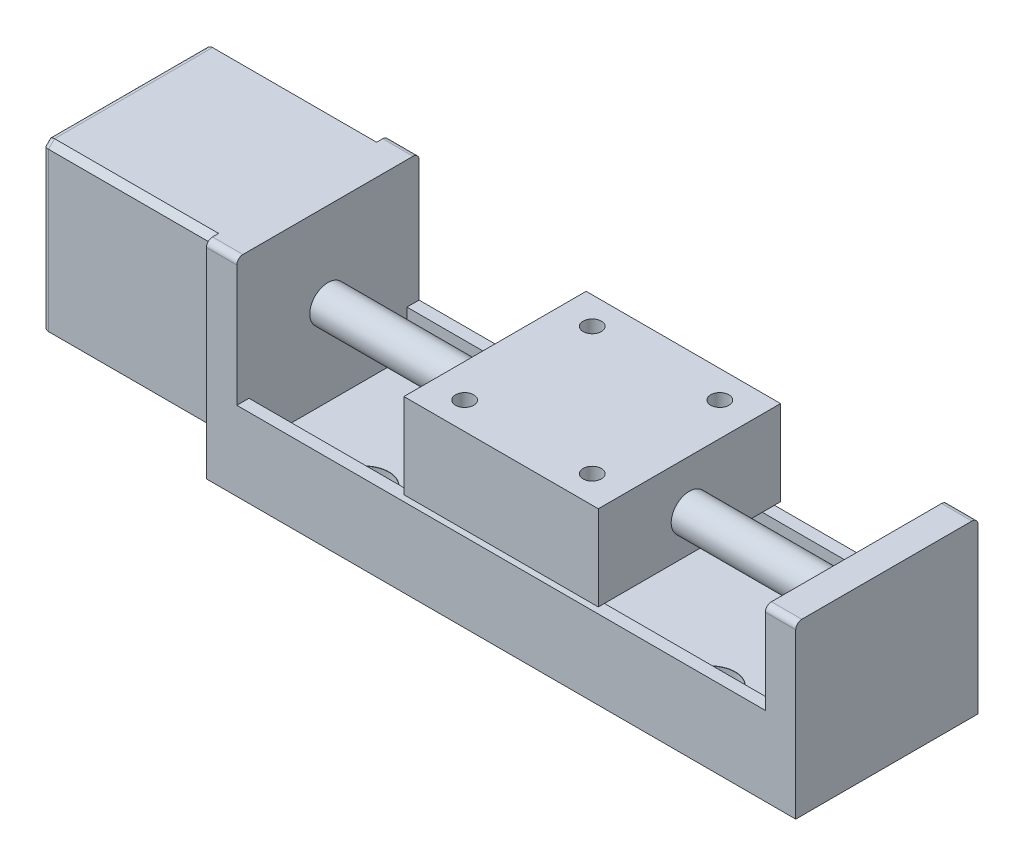
SolidWorks part; units mm, degrees
material "1060 Alloy"
ref_plane "Front Plane" through (0, 0, 0) normal (0, 0, 1) x (1, 0, 0)
ref_plane "Top Plane" through (0, 0, 0) normal (0, 1, 0) x (1, 0, 0)
ref_plane "Right Plane" through (0, 0, 0) normal (1, 0, 0) x (0, 0, -1)
sketch "Sketch1" plane through (0, 0, 0) normal (0, 0, 1) x (1, 0, 0)
  line L0 (-78.5, 34) -> (-78.5, 6)
  line L1 (-78.5, 6) -> (-48.5, 6)
  line L2 (-48.5, 6) -> (-48.5, 0)
  line L3 (-48.5, 0) -> (48.5, 0)
  line L4 (48.5, 0) -> (48.5, 28)
  line L5 (48.5, 28) -> (43.5, 28)
  line L6 (43.5, 28) -> (43.5, 13)
  line L7 (43.5, 13) -> (-43.5, 13)
  line L8 (-43.5, 13) -> (-43.5, 34)
  line L11 (-43.5, 34) -> (-78.5, 34)
  point P0 (-20.9434, 30.6111)
  point P11 (0, 0)
  point P13 (-49.3333, 26.9444)
  dimension "D1" = 5
  dimension "D2" = 5
  dimension "D3" = 13
  dimension "D4" = 28
  dimension "D5" = 30
  dimension "D6" = 28
  dimension "D7" = 34
  dimension "D8" = 127
extrude "Boss-Extrude1" add sketch "Sketch1" along normal mid plane 30
sketch "Sketch2" plane through (0, 13, 0) normal (0, 1, 0) x (1, 0, 0)
  line L0 (-43.5, -15) -> (-43.5, 15) construction
  line L1 (-43.5, -13) -> (43.5, -13)
  line L2 (-43.5, -13) -> (-43.5, 13)
  line L3 (-43.5, 13) -> (43.5, 13)
  line L4 (43.5, -13) -> (43.5, 13)
  line L5 (-43.5, -13) -> (43.5, 13) construction
  line L6 (-43.5, 13) -> (43.5, -13) construction
  line L7 (43.5, -15) -> (-43.5, -15) construction
  point P0 (0, 0)
  dimension "D1" = 2
extrude "Cut-Extrude1" cut sketch "Sketch2" against normal offset from surface (7 mm away) 6 up to face at (0, 0, 0)
sketch "Sketch3" plane through (48.5, 0, 0) normal (1, 0, 0) x (0, 0, -1)
  circle A0 centre (0, 20) radius 3
  point P2 (0, 0)
  dimension "D1" = 20
  dimension "D2" = 6
extrude "Boss-Extrude2" add sketch "Sketch3" against normal up to surface (92 mm away) up to face at (-43.5, 16.5, 0)
sketch "Sketch4" plane through (0, 34, 0) normal (0, 1, 0) x (1, 0, 0)
  line L0 (-48.5, 14) -> (-48.5, -14) construction
  line L3 (-48.5, -14) -> (-76.5, -14)
  line L4 (-76.5, -14) -> (-76.5, 14)
  line L5 (-76.5, 14) -> (-48.5, 14)
  line L6 (-43.5, -13) -> (-43.5, 13) construction
  line L7 (-43.5, 0) -> (-48.5, 0) construction
  line L8 (-43.5, -15) -> (-43.5, 15) construction
  line L9 (-48.5, -14) -> (-48.5, -15)
  line L10 (-43.5, -15) -> (-78.5, -15) construction
  line L11 (-48.5, -15) -> (-78.5, -15)
  line L12 (-78.5, -15) -> (-78.5, 15)
  line L13 (-78.5, 15) -> (-48.5, 15)
  line L14 (-43.5, 15) -> (-78.5, 15) construction
  line L15 (-48.5, 15) -> (-48.5, 14)
  line M7 (-43.5, 15) -> (-78.5, 15)
  line M8 (-78.5, 15) -> (-78.5, -15)
  line M9 (-78.5, -15) -> (-43.5, -15)
  dimension "D1" = 5
  dimension "D2" = 28
  dimension "D3" = 28
extrude "Cut-Extrude2" cut sketch "Sketch4" against normal through all contours L15 L9 L3 L4 L5 M7 M8 M9 | L4 L5 L15 L13 L12 L11 L9 L3 region at (-48.9243, 34, 14.5)
chamfer "Chamfer1" distance 1 angle 45 4 edges at (-62.5, 6, 14) (-62.5, 6, -14) (-62.5, 34, -14) (-62.5, 34, 14)
fillet "Fillet1" radius 1 8 edges at (-76.5, 6.5, -13.5) (-76.5, 20, -14) (-76.5, 33.5, -13.5) (-76.5, 34, 0) (-76.5, 33.5, 13.5) (-76.5, 20, 14) (-76.5, 6.5, 13.5) (-76.5, 6, 0)
fillet "Fillet2" radius 1 4 edges at (46, 28, 15) (46, 28, -15) (-46, 34, -15) (-46, 34, 15)
hole_wizard "CBORE for M4 Hex Socket Head Cap Screw1" positions "Sketch5" profile "Sketch6" counterbore size "M4" standard "ISO" end condition through all
sketch "Sketch5" plane through (0, 6, 0) normal (0, 1, 0) x (1, 0, 0)
  line L0 (-28.5, 8.0068) -> (28.5, 8.0068) construction
  line L1 (28.5, 8.0068) -> (28.5, -8.9932) construction
  line L2 (28.5, -8.9932) -> (-28.5, -8.9932) construction
  line L3 (-28.5, -8.9932) -> (-28.5, 8.0068) construction
  line L5 (43.5, -14) -> (43.5, 14) construction
  line L6 (-43.5, -13) -> (-43.5, 13) construction
  point P0 (-28.5, 8.0068)
  point P2 (-28.5, -8.9932)
  point P4 (28.5, 8.0068)
  point P6 (28.5, -8.9932)
  dimension "D1" = 17
  dimension "D2" = 15
  dimension "D3" = 15
sketch "Sketch6" plane through (-28.5, 6, -8.0068) normal (1, 0, 0) x (0, 0, 1)
  line L0 (0, 0) -> (0, 6)
  line L1 (0, 6) -> (2.25, 6)
  line L3 (2.25, 6) -> (2.25, 4.4)
  line L4 (4, 4.4) -> (2.25, 4.4)
  line L5 (4, 4.4) -> (4, 0.025)
  line L6 (4, 0.025) -> (4.025, 0)
  line L7 (4.025, 0) -> (0, 0)
  line L8 (-4, 0.025) -> (-4.025, 0) construction
  line L11 (0, -6.35) -> (0, 107.95) construction
  dimension "Thru Hole Dia." = 4.5
  dimension "Thru Hole Depth" = 6
  dimension "C'Bore Dia." = 8
  dimension "C'Bore Depth" = 4.4
  dimension "Near C'Sink Dia." = 8.05
  dimension "Near C'Sink Angle" = 90
sketch "Sketch7" plane through (0, 28, 0) normal (0, 1, 0) x (1, 0, 0)
  line L1 (-16, -15) -> (16, -15)
  line L2 (-16, -15) -> (-16, 15)
  line L3 (-16, 15) -> (16, 15)
  line L4 (16, -15) -> (16, 15)
  line L5 (-16, -15) -> (16, 15) construction
  line L6 (-16, 15) -> (16, -15) construction
  point P0 (0, 0)
  dimension "D1" = 30
  dimension "D2" = 32
extrude "Boss-Extrude3" add sketch "Sketch7" against normal offset from surface (14 mm away) 1 up to face at (0, 13, 14)
sketch "Sketch8" plane through (0, 28, 0) normal (0, 1, 0) x (1, 0, 0)
  line L0 (-10.5, 10.5) -> (10.5, 10.5) construction
  line L1 (10.5, 10.5) -> (10.5, -10.5) construction
  line L2 (10.5, -10.5) -> (-10.5, -10.5) construction
  line L3 (-10.5, -10.5) -> (-10.5, 10.5) construction
  line L4 (16, 15) -> (-16, 15) construction
  line L5 (-16, 15) -> (-16, -15) construction
  circle A0 centre (-10.5, 10.5) radius 1.5 construction
  circle A1 centre (10.5, 10.5) radius 1.5 construction
  circle A2 centre (10.5, -10.5) radius 1.5 construction
  circle A3 centre (-10.5, -10.5) radius 1.5 construction
  dimension "D1" = 3
  dimension "D2" = 18
  dimension "D3" = 18
  dimension "D4" = 3
  dimension "D5" = 4
hole_wizard "Hole1" positions "Sketch9" profile "Sketch10" legacy
sketch "Sketch9" plane through (0, 28, 0) normal (0, 1, 0) x (1, 0, 0)
  point P0 (10.5, 10.5)
  point P3 (10.5, -10.5)
  point P6 (-10.5, -10.5)
  point P9 (-10.5, 10.5)
sketch "Sketch10" plane through (10.5, 28, -10.5) normal (1, 0, 0) x (0, 0, 1)
  line L0 (0, 0) -> (0, 6)
  line L1 (0, 6) -> (1.5, 6)
  line L2 (1.5, 6) -> (1.5, 0)
  line L3 (1.5, 0) -> (0, 0)
  line L4 (0, 110) -> (0, -10) construction
  dimension "Diameter" = 3
  dimension "Depth" = 6
